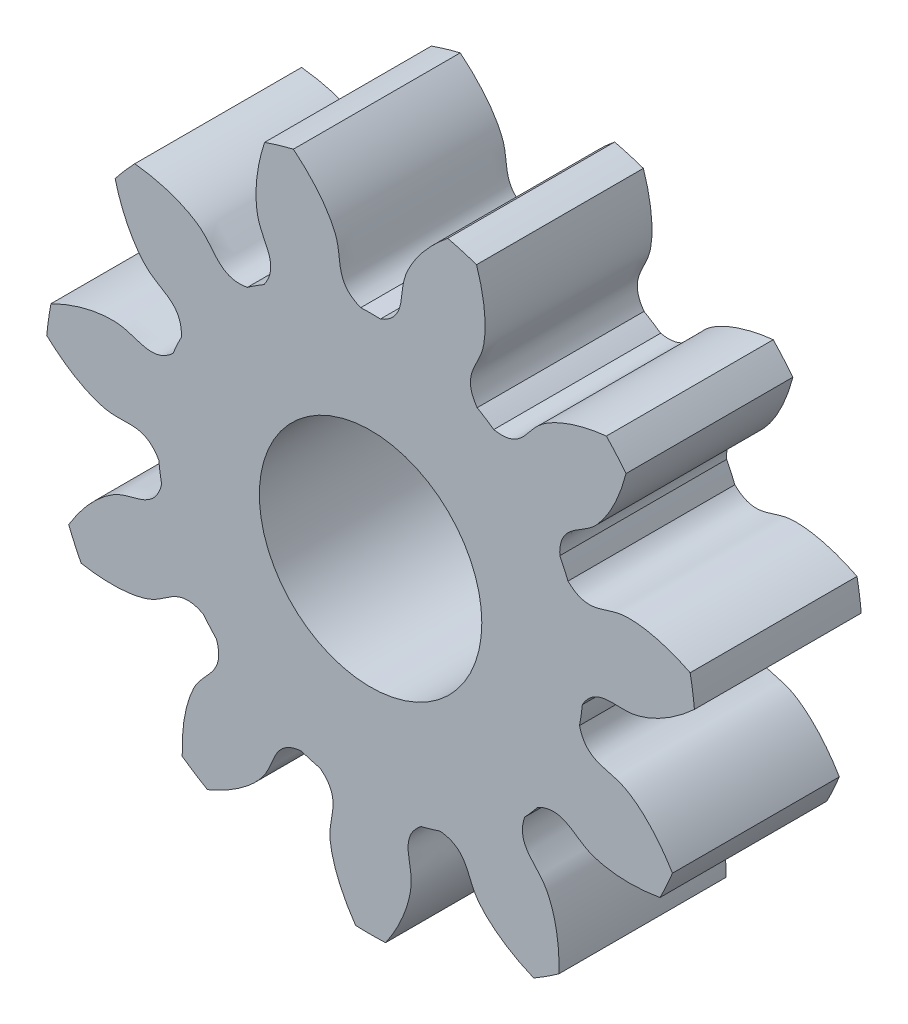
SolidWorks part; units mm, degrees
ref_plane "前视基准面" through (0, 0, 0) normal (0, 0, 1) x (1, 0, 0)
ref_plane "上视基准面" through (0, 0, 0) normal (0, 1, 0) x (1, 0, 0)
ref_plane "右视基准面" through (0, 0, 0) normal (1, 0, 0) x (0, 0, -1)
other "Configuration Table"
sketch "草图1" plane through (0, 0, 0) normal (0, 0, 1) x (1, 0, 0)
  circle A0 centre (0, 0) radius 2.925
extrude "凸台-拉伸1" add sketch "草图1" along normal blind 1.5
ref_axis "基准轴1" through (0, 0, 1.5) along (0, 0, -1)
sketch "草图2" plane through (0, 0, 0) normal (0, 0, 1) x (1, 0, 0)
  line L0 (0, 0) -> (0, 2.925) construction
  circle A0 centre (0, 0) radius 2.925 construction
  arc A1 (0.0885, 1.9104) -> (-0.0885, 1.9104) centre (0, 0) ccw
  arc A2 (1.6426, 3.2805) -> (-1.6426, 3.2805) centre (0, 0) ccw
  spline S0 degree 3 poles (0.0885, 1.9104) (0.3157, 2.001) (0.2586, 2.1861) (0.3071, 2.3434) (0.3099, 2.3518) (0.3131, 2.361) (0.3169, 2.371) (0.3212, 2.3818) (0.326, 2.3934) (0.3315, 2.4057) (0.3376, 2.4188) (0.3444, 2.4325) (0.3519, 2.447) (0.3602, 2.4621) (0.3692, 2.4779) (0.3789, 2.4942) (0.3895, 2.5112) (0.401, 2.5287) (0.4133, 2.5468) (0.4265, 2.5654) (0.4407, 2.5844) (0.4558, 2.6039) (0.4718, 2.6238) (0.4889, 2.6441) (0.5069, 2.6648) (0.526, 2.6858) (0.5462, 2.707) (0.5674, 2.7286) (0.5898, 2.7503) (0.6132, 2.7722) (0.6378, 2.7943) (0.6635, 2.8165) (0.6903, 2.8388) (0.7183, 2.8611) (0.7475, 2.8834) (0.7779, 2.9057) (0.8095, 2.9279) (0.8423, 2.9499) (0.8764, 2.9718) (0.9116, 2.9936) (0.9481, 3.015) (0.9858, 3.0363) (1.0247, 3.0571) (1.0649, 3.0777) (1.1063, 3.0978) (1.149, 3.1175) (1.1929, 3.1367) (1.238, 3.1554) (1.2844, 3.1735) (1.332, 3.191) (1.3808, 3.2078) (1.4308, 3.224) (1.482, 3.2394) (1.5525, 3.2591) (1.6063, 3.2723) (1.6426, 3.2805) knots 0 0 0 0 0.219011 0.222642 0.226699 0.231184 0.236096 0.241435 0.247201 0.253394 0.260015 0.267062 0.274537 0.282438 0.290767 0.299523 0.308706 0.318316 0.328354 0.338818 0.34971 0.361028 0.372774 0.384947 0.397547 0.410574 0.424029 0.43791 0.452219 0.466954 0.482117 0.497707 0.513724 0.530168 0.547039 0.564338 0.582063 0.600216 0.618795 0.637802 0.657236 0.677097 0.697385 0.718101 0.739243 0.760813 0.782809 0.805233 0.828084 0.851362 0.875067 0.8992 0.923759 0.948746 1 1 1 1
  spline S1 degree 3 poles (-0.0885, 1.9104) (-0.3157, 2.001) (-0.2586, 2.1861) (-0.3071, 2.3434) (-0.3099, 2.3518) (-0.3131, 2.361) (-0.3169, 2.371) (-0.3212, 2.3818) (-0.326, 2.3934) (-0.3315, 2.4057) (-0.3376, 2.4188) (-0.3444, 2.4325) (-0.3519, 2.447) (-0.3602, 2.4621) (-0.3692, 2.4779) (-0.3789, 2.4942) (-0.3895, 2.5112) (-0.401, 2.5287) (-0.4133, 2.5468) (-0.4265, 2.5654) (-0.4407, 2.5844) (-0.4558, 2.6039) (-0.4718, 2.6238) (-0.4889, 2.6441) (-0.5069, 2.6648) (-0.526, 2.6858) (-0.5462, 2.707) (-0.5674, 2.7286) (-0.5898, 2.7503) (-0.6132, 2.7722) (-0.6378, 2.7943) (-0.6635, 2.8165) (-0.6903, 2.8388) (-0.7183, 2.8611) (-0.7475, 2.8834) (-0.7779, 2.9057) (-0.8095, 2.9279) (-0.8423, 2.9499) (-0.8764, 2.9718) (-0.9116, 2.9936) (-0.9481, 3.015) (-0.9858, 3.0363) (-1.0247, 3.0571) (-1.0649, 3.0777) (-1.1063, 3.0978) (-1.149, 3.1175) (-1.1929, 3.1367) (-1.238, 3.1554) (-1.2844, 3.1735) (-1.332, 3.191) (-1.3808, 3.2078) (-1.4308, 3.224) (-1.482, 3.2394) (-1.5525, 3.2591) (-1.6063, 3.2723) (-1.6426, 3.2805) knots 0 0 0 0 0.219011 0.222642 0.226699 0.231184 0.236096 0.241435 0.247201 0.253394 0.260015 0.267062 0.274537 0.282438 0.290767 0.299523 0.308706 0.318316 0.328354 0.338818 0.34971 0.361028 0.372774 0.384947 0.397547 0.410574 0.424029 0.43791 0.452219 0.466954 0.482117 0.497707 0.513724 0.530168 0.547039 0.564338 0.582063 0.600216 0.618795 0.637802 0.657236 0.677097 0.697385 0.718101 0.739243 0.760813 0.782809 0.805233 0.828084 0.851362 0.875067 0.8992 0.923759 0.948746 1 1 1 1
extrude "切除-拉伸1" cut sketch "草图2" along normal through all
pattern_circular "阵列(圆周)1" count 11 every 32.727 about axis through (0, 0, 1.5) along (0, 0, -1) of "切除-拉伸1"
sketch "草图3" plane through (0, 0, 0) normal (0, 0, 1) x (1, 0, 0)
  circle A0 centre (0, 0) radius 2.475 construction
  dimension "Dn" = 4.95
sketch "草图4" plane through (0, 0, 1.5) normal (0, 0, 1) x (1, 0, 0)
  circle A0 centre (0, 0) radius 1
  dimension "D1" = 2
extrude "切除-拉伸2" cut sketch "草图4" against normal through all
